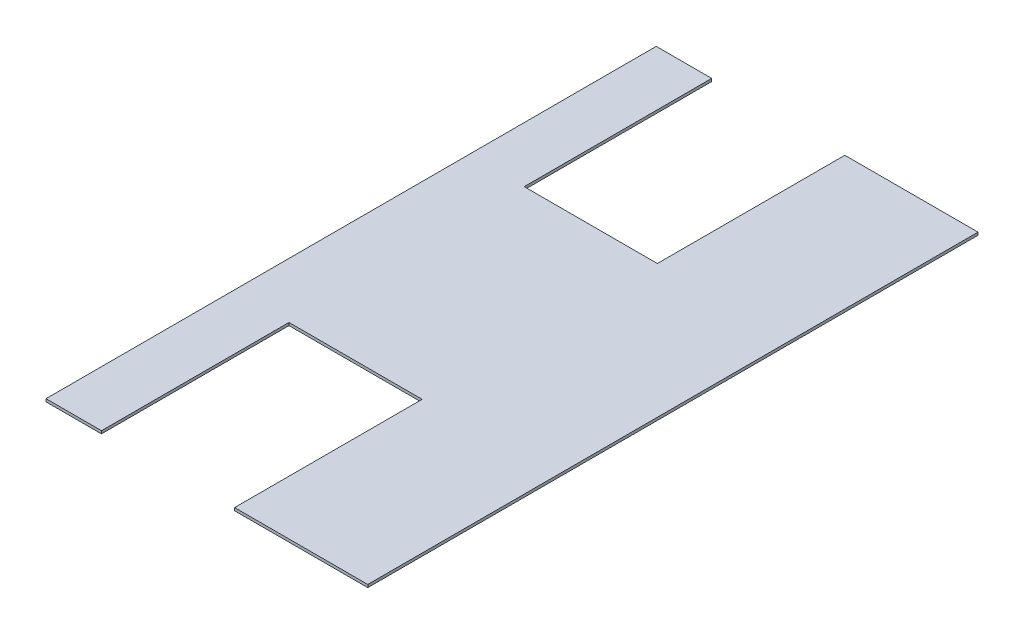
SolidWorks part; units mm, degrees
ref_plane "Front Plane" through (0, 0, 0) normal (0, 0, 1) x (1, 0, 0)
ref_plane "Top Plane" through (0, 0, 0) normal (0, 1, 0) x (1, 0, 0)
ref_plane "Right Plane" through (0, 0, 0) normal (1, 0, 0) x (0, 0, -1)
sketch "Sketch1" plane through (0, 0, 0) normal (0, 1, 0) x (1, 0, 0)
  line L0 (-195.9659, 446.3263) -> (-43.5659, 446.3263)
  line L1 (-411.8659, 446.3263) -> (-348.3659, 446.3263)
  line L2 (-411.8659, 446.3263) -> (-411.8659, -252.1737)
  line L3 (-411.8659, -252.1737) -> (-348.3659, -252.1737)
  line L4 (-43.5659, 446.3263) -> (-43.5659, -252.1737)
  line L6 (-195.9659, -252.1737) -> (-195.9659, -37.5437)
  line L7 (-195.9659, -37.5437) -> (-348.3659, -37.5437)
  line L8 (-348.3659, -252.1737) -> (-348.3659, -37.5437)
  line L9 (-195.9659, -252.1737) -> (-43.5659, -252.1737)
  line L10 (-195.9659, 446.3263) -> (-195.9659, 231.6963)
  line L11 (-195.9659, 231.6963) -> (-348.3659, 231.6963)
  line L12 (-348.3659, 446.3263) -> (-348.3659, 231.6963)
  dimension "D1" = 368.3
  dimension "D2" = 698.5
  dimension "D3" = 63.5
  dimension "D4" = 63.5
  dimension "D5" = 152.4
  dimension "D6" = 152.4
  dimension "D7" = 214.63
  dimension "D8" = 214.63
extrude "Boss-Extrude1" add sketch "Sketch1" along normal blind 3.175
